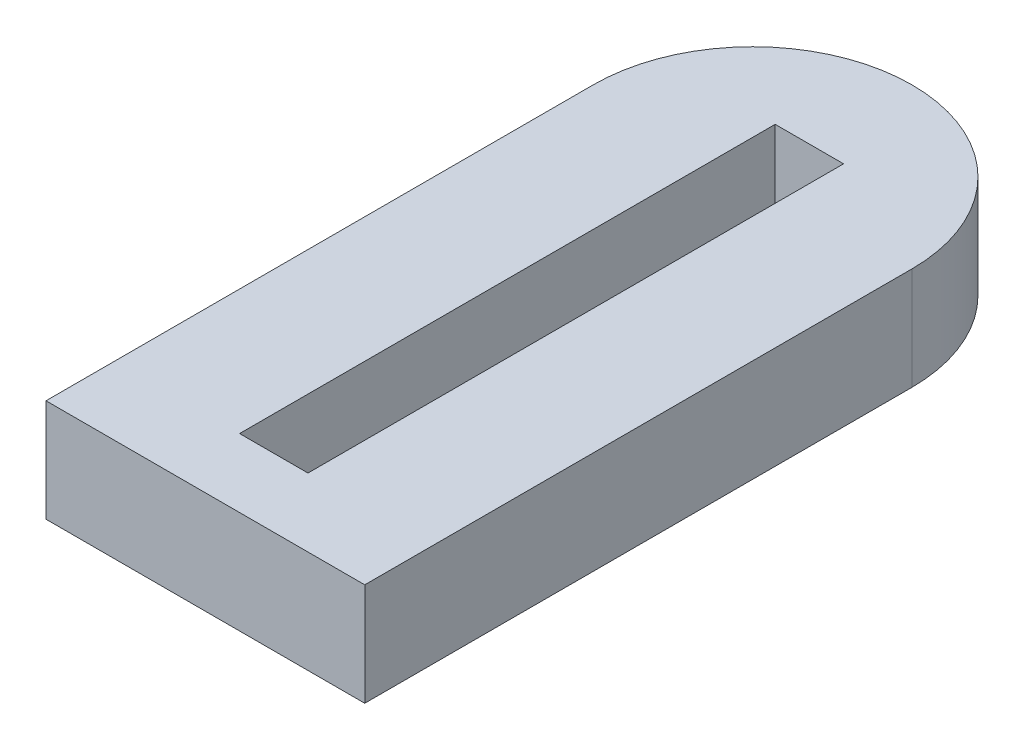
SolidWorks part; units mm, degrees
ref_plane "Front Plane" through (0, 0, 0) normal (0, 0, 1) x (1, 0, 0)
ref_plane "Top Plane" through (0, 0, 0) normal (0, 1, 0) x (1, 0, 0)
ref_plane "Right Plane" through (0, 0, 0) normal (1, 0, 0) x (0, 0, -1)
ref_axis "Axis2" through (0, 0, 6.5595) along (0, 0, -1)
sketch "Sketch1" plane through (0, 0, 0) normal (0, 1, 0) x (1, 0, 0)
  line L0 (-59.182, 0) -> (0, 0)
  line L1 (-59.182, 0) -> (-59.182, 101.6)
  line L2 (-35.941, 12.7) -> (-23.241, 12.7)
  line L3 (0, 101.6) -> (0, 0)
  line L4 (-23.241, 12.7) -> (-23.241, 112.141)
  line L5 (-23.241, 112.141) -> (-35.941, 112.141)
  line L6 (-35.941, 112.141) -> (-35.941, 12.7)
  line L7 (0, -6.5595) -> (0, 137.7505) construction
  arc A0 (-59.182, 101.6) -> (0, 101.6) centre (-29.591, 101.6) cw
  point P9 (-29.591, 12.7)
  point P11 (-29.591, 0)
  point P12 (-29.591, 131.191)
  dimension "D1" = 59.182
  dimension "D2" = 12.7
  dimension "D3" = 101.6
  dimension "D4" = 12.7
  dimension "D5" = 19.05
extrude "Boss-Extrude1" add sketch "Sketch1" along normal blind 19.05
